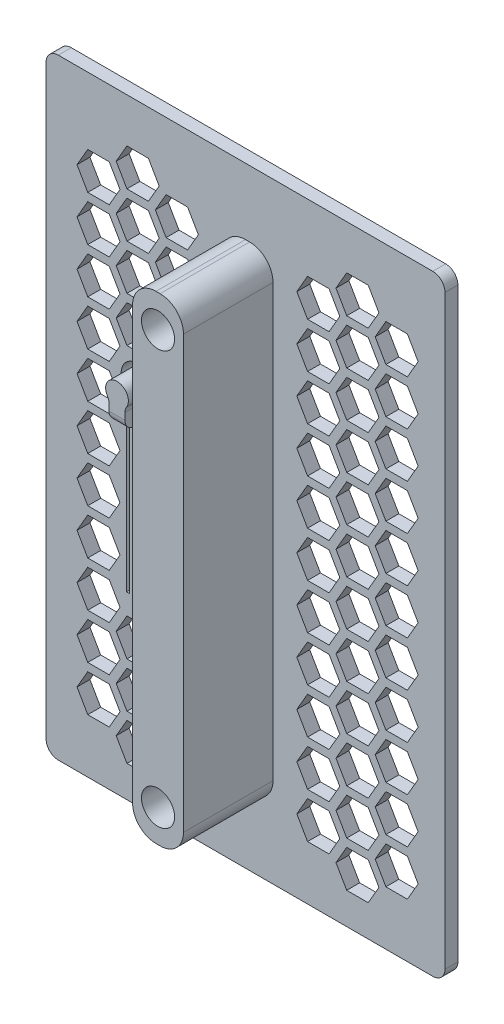
SolidWorks part; units mm, degrees
ref_plane "Front Plane" through (0, 0, 0) normal (0, 0, 1) x (1, 0, 0)
ref_plane "Top Plane" through (0, 0, 0) normal (0, 1, 0) x (1, 0, 0)
ref_plane "Right Plane" through (0, 0, 0) normal (1, 0, 0) x (0, 0, -1)
sketch "Sketch1" plane through (0, 0, 0) normal (0, 0, 1) x (1, 0, 0)
  line L0 (24.5, 37.5) -> (-24.5, 37.5) construction
  line L1 (24.5, -37.5) -> (-24.5, -37.5)
  line L2 (24.5, -37.5) -> (24.5, 37.5)
  line L3 (24.5, 37.5) -> (-24.5, 37.5)
  line L4 (-24.5, -37.5) -> (-24.5, 37.5)
  line L5 (24.5, -37.5) -> (-24.5, 37.5) construction
  line L6 (24.5, 37.5) -> (-24.5, -37.5) construction
  line L7 (24.5, 37.5) -> (24.5, -37.5) construction
  point P0 (0, 0)
extrude "Boss-Extrude1" add sketch "Sketch1" along normal blind 1.5875
sketch "Sketch2" plane through (0, 0, 1.5875) normal (0, 0, 1) x (1, 0, 0)
  line L69 (0, -29.373) -> (0.5, -29.373)
  line L70 (3.373, -26.5) -> (3.373, 26.5)
  line L71 (0.5, 29.373) -> (0, 29.373)
  line L72 (-2.873, 26.5) -> (-2.873, -26.5)
  line L73 (0, -29.373) -> (0.5, -29.373)
  line L74 (3.373, -26.5) -> (3.373, 26.5)
  line L75 (0.5, 29.373) -> (0, 29.373)
  line L76 (-2.873, 26.5) -> (-2.873, -26.5)
  arc A54 (0.5, -29.373) -> (3.373, -26.5) centre (0.5, -26.5) ccw
  arc A55 (-2.873, -26.5) -> (0, -29.373) centre (0, -26.5) ccw
  arc A56 (3.373, 26.5) -> (0.5, 29.373) centre (0.5, 26.5) ccw
  arc A57 (0, 29.373) -> (-2.873, 26.5) centre (0, 26.5) ccw
  arc A58 (0.5, -29.373) -> (3.373, -26.5) centre (0.5, -26.5) ccw
  arc A59 (-2.873, -26.5) -> (0, -29.373) centre (0, -26.5) ccw
  arc A60 (3.373, 26.5) -> (0.5, 29.373) centre (0.5, 26.5) ccw
  arc A61 (0, 29.373) -> (-2.873, 26.5) centre (0, 26.5) ccw
  dimension "D1" = 0.127
extrude "Boss-Extrude2" add sketch "Sketch2" along normal up to surface (11 mm away)
sketch "Sketch3" plane through (0, 0, 12.5875) normal (0, 0, 1) x (1, 0, 0)
  line L0 (0, 29.373) -> (0.5, 29.373) construction
  line L1 (0.25, 25.4) -> (0, 0) construction
  line L2 (0, 0) -> (0.25, -25.4) construction
  circle A0 centre (0.25, 25.4) radius 2.032
  circle A1 centre (0.25, -25.4) radius 2.032
  point P6 (0.25, 29.373)
  dimension "D1" = 4.064
  dimension "D2" = 25.4
extrude "Cut-Extrude1" cut sketch "Sketch3" against normal blind 9.525
fillet "Fillet1" radius 1.5 4 edges at (24.5, -37.5, 0.7937) (-24.5, -37.5, 0.7937) (-24.5, 37.5, 0.7937) (24.5, 37.5, 0.7937)
sketch "Sketch4" plane through (0, 0, 0) normal (0, 0, -1) x (-1, 0, 0)
  line L0 (-18.5619, -28.5679) -> (-13.75, -31.346) construction
  line L1 (-16.3896, -31.346) -> (-15.0698, -33.632)
  line L2 (-15.0698, -33.632) -> (-12.4302, -33.632)
  line L3 (-12.4302, -33.632) -> (-11.1104, -31.346)
  line L4 (-11.1104, -31.346) -> (-12.4302, -29.06)
  line L5 (-12.4302, -29.06) -> (-15.0698, -29.06)
  line L6 (-15.0698, -29.06) -> (-16.3896, -31.346)
  line L7 (-21.2015, -28.5679) -> (-19.8817, -30.8539)
  line L8 (-19.8817, -30.8539) -> (-17.242, -30.8539)
  line L9 (-17.242, -30.8539) -> (-15.9222, -28.5679)
  line L10 (-15.9222, -28.5679) -> (-17.242, -26.2819)
  line L11 (-17.242, -26.2819) -> (-19.8817, -26.2819)
  line L12 (-19.8817, -26.2819) -> (-21.2015, -28.5679)
  line L13 (-10.258, -30.8539) -> (-7.6183, -30.8539)
  line L14 (-7.6183, -30.8539) -> (-6.2985, -28.5679)
  line L15 (-6.2985, -28.5679) -> (-7.6183, -26.2819)
  line L16 (-7.6183, -26.2819) -> (-10.258, -26.2819)
  line L17 (-10.258, -26.2819) -> (-11.5778, -28.5679)
  line L18 (-11.5778, -28.5679) -> (-10.258, -30.8539)
  line L19 (-11.1104, -31.346) -> (-10.258, -30.8539) construction
  line L20 (-13.75, -31.346) -> (-8.9381, -28.5679) construction
  line L21 (-4.5, -26.832) -> (-23, -26.832) construction
  line L22 (-10.258, -20.7257) -> (-11.5778, -23.0117)
  line L23 (-7.6183, -20.7257) -> (-10.258, -20.7257)
  line L24 (-6.2985, -23.0117) -> (-7.6183, -20.7257)
  line L25 (-7.6183, -25.2977) -> (-6.2985, -23.0117)
  line L26 (-10.258, -25.2977) -> (-7.6183, -25.2977)
  line L27 (-11.5778, -23.0117) -> (-10.258, -25.2977)
  line L28 (-11.1104, -25.7898) -> (-12.4302, -23.5038)
  line L29 (-12.4302, -23.5038) -> (-15.0698, -23.5038)
  line L30 (-15.0698, -23.5038) -> (-16.3896, -25.7898)
  line L31 (-16.3896, -25.7898) -> (-15.0698, -28.0758)
  line L32 (-15.0698, -28.0758) -> (-12.4302, -28.0758)
  line L33 (-12.4302, -28.0758) -> (-11.1104, -25.7898)
  line L34 (-17.242, -25.2977) -> (-15.9222, -23.0117)
  line L35 (-15.9222, -23.0117) -> (-17.242, -20.7257)
  line L36 (-17.242, -20.7257) -> (-19.8817, -20.7257)
  line L37 (-19.8817, -20.7257) -> (-21.2015, -23.0117)
  line L38 (-21.2015, -23.0117) -> (-19.8817, -25.2977)
  line L39 (-19.8817, -25.2977) -> (-17.242, -25.2977)
  line L40 (-10.258, -15.1694) -> (-11.5778, -17.4554)
  line L41 (-7.6183, -15.1694) -> (-10.258, -15.1694)
  line L42 (-6.2985, -17.4554) -> (-7.6183, -15.1694)
  line L43 (-7.6183, -19.7414) -> (-6.2985, -17.4554)
  line L44 (-10.258, -19.7414) -> (-7.6183, -19.7414)
  line L45 (-11.5778, -17.4554) -> (-10.258, -19.7414)
  line L46 (-11.1104, -20.2335) -> (-12.4302, -17.9475)
  line L47 (-12.4302, -17.9475) -> (-15.0698, -17.9475)
  line L48 (-15.0698, -17.9475) -> (-16.3896, -20.2335)
  line L49 (-16.3896, -20.2335) -> (-15.0698, -22.5195)
  line L50 (-15.0698, -22.5195) -> (-12.4302, -22.5195)
  line L51 (-12.4302, -22.5195) -> (-11.1104, -20.2335)
  line L52 (-17.242, -19.7414) -> (-15.9222, -17.4554)
  line L53 (-15.9222, -17.4554) -> (-17.242, -15.1694)
  line L54 (-17.242, -15.1694) -> (-19.8817, -15.1694)
  line L55 (-19.8817, -15.1694) -> (-21.2015, -17.4554)
  line L56 (-21.2015, -17.4554) -> (-19.8817, -19.7414)
  line L57 (-19.8817, -19.7414) -> (-17.242, -19.7414)
  line L58 (-10.258, -9.6132) -> (-11.5778, -11.8992)
  line L59 (-7.6183, -9.6132) -> (-10.258, -9.6132)
  line L60 (-6.2985, -11.8992) -> (-7.6183, -9.6132)
  line L61 (-7.6183, -14.1852) -> (-6.2985, -11.8992)
  line L62 (-10.258, -14.1852) -> (-7.6183, -14.1852)
  line L63 (-11.5778, -11.8992) -> (-10.258, -14.1852)
  line L64 (-11.1104, -14.6773) -> (-12.4302, -12.3913)
  line L65 (-12.4302, -12.3913) -> (-15.0698, -12.3913)
  line L66 (-15.0698, -12.3913) -> (-16.3896, -14.6773)
  line L67 (-16.3896, -14.6773) -> (-15.0698, -16.9633)
  line L68 (-15.0698, -16.9633) -> (-12.4302, -16.9633)
  line L69 (-12.4302, -16.9633) -> (-11.1104, -14.6773)
  line L70 (-17.242, -14.1852) -> (-15.9222, -11.8992)
  line L71 (-15.9222, -11.8992) -> (-17.242, -9.6132)
  line L72 (-17.242, -9.6132) -> (-19.8817, -9.6132)
  line L73 (-19.8817, -9.6132) -> (-21.2015, -11.8992)
  line L74 (-21.2015, -11.8992) -> (-19.8817, -14.1852)
  line L75 (-19.8817, -14.1852) -> (-17.242, -14.1852)
  line L76 (-10.258, -4.0569) -> (-11.5778, -6.3429)
  line L77 (-7.6183, -4.0569) -> (-10.258, -4.0569)
  line L78 (-6.2985, -6.3429) -> (-7.6183, -4.0569)
  line L79 (-7.6183, -8.6289) -> (-6.2985, -6.3429)
  line L80 (-10.258, -8.6289) -> (-7.6183, -8.6289)
  line L81 (-11.5778, -6.3429) -> (-10.258, -8.6289)
  line L82 (-11.1104, -9.121) -> (-12.4302, -6.835)
  line L83 (-12.4302, -6.835) -> (-15.0698, -6.835)
  line L84 (-15.0698, -6.835) -> (-16.3896, -9.121)
  line L85 (-16.3896, -9.121) -> (-15.0698, -11.407)
  line L86 (-15.0698, -11.407) -> (-12.4302, -11.407)
  line L87 (-12.4302, -11.407) -> (-11.1104, -9.121)
  line L88 (-17.242, -8.6289) -> (-15.9222, -6.3429)
  line L89 (-15.9222, -6.3429) -> (-17.242, -4.0569)
  line L90 (-17.242, -4.0569) -> (-19.8817, -4.0569)
  line L91 (-19.8817, -4.0569) -> (-21.2015, -6.3429)
  line L92 (-21.2015, -6.3429) -> (-19.8817, -8.6289)
  line L93 (-19.8817, -8.6289) -> (-17.242, -8.6289)
  line L94 (-10.258, 1.4993) -> (-11.5778, -0.7867)
  line L95 (-7.6183, 1.4993) -> (-10.258, 1.4993)
  line L96 (-6.2985, -0.7867) -> (-7.6183, 1.4993)
  line L97 (-7.6183, -3.0727) -> (-6.2985, -0.7867)
  line L98 (-10.258, -3.0727) -> (-7.6183, -3.0727)
  line L99 (-11.5778, -0.7867) -> (-10.258, -3.0727)
  line L100 (-11.1104, -3.5648) -> (-12.4302, -1.2788)
  line L101 (-12.4302, -1.2788) -> (-15.0698, -1.2788)
  line L102 (-15.0698, -1.2788) -> (-16.3896, -3.5648)
  line L103 (-16.3896, -3.5648) -> (-15.0698, -5.8508)
  line L104 (-15.0698, -5.8508) -> (-12.4302, -5.8508)
  line L105 (-12.4302, -5.8508) -> (-11.1104, -3.5648)
  line L106 (-17.242, -3.0727) -> (-15.9222, -0.7867)
  line L107 (-15.9222, -0.7867) -> (-17.242, 1.4993)
  line L108 (-17.242, 1.4993) -> (-19.8817, 1.4993)
  line L109 (-19.8817, 1.4993) -> (-21.2015, -0.7867)
  line L110 (-21.2015, -0.7867) -> (-19.8817, -3.0727)
  line L111 (-19.8817, -3.0727) -> (-17.242, -3.0727)
  line L112 (-10.258, 7.0556) -> (-11.5778, 4.7696)
  line L113 (-7.6183, 7.0556) -> (-10.258, 7.0556)
  line L114 (-6.2985, 4.7696) -> (-7.6183, 7.0556)
  line L115 (-7.6183, 2.4836) -> (-6.2985, 4.7696)
  line L116 (-10.258, 2.4836) -> (-7.6183, 2.4836)
  line L117 (-11.5778, 4.7696) -> (-10.258, 2.4836)
  line L118 (-11.1104, 1.9915) -> (-12.4302, 4.2775)
  line L119 (-12.4302, 4.2775) -> (-15.0698, 4.2775)
  line L120 (-15.0698, 4.2775) -> (-16.3896, 1.9915)
  line L121 (-16.3896, 1.9915) -> (-15.0698, -0.2945)
  line L122 (-15.0698, -0.2945) -> (-12.4302, -0.2945)
  line L123 (-12.4302, -0.2945) -> (-11.1104, 1.9915)
  line L124 (-17.242, 2.4836) -> (-15.9222, 4.7696)
  line L125 (-15.9222, 4.7696) -> (-17.242, 7.0556)
  line L126 (-17.242, 7.0556) -> (-19.8817, 7.0556)
  line L127 (-19.8817, 7.0556) -> (-21.2015, 4.7696)
  line L128 (-21.2015, 4.7696) -> (-19.8817, 2.4836)
  line L129 (-19.8817, 2.4836) -> (-17.242, 2.4836)
  line L130 (-10.258, 12.6118) -> (-11.5778, 10.3258)
  line L131 (-7.6183, 12.6118) -> (-10.258, 12.6118)
  line L132 (-6.2985, 10.3258) -> (-7.6183, 12.6118)
  line L133 (-7.6183, 8.0398) -> (-6.2985, 10.3258)
  line L134 (-10.258, 8.0398) -> (-7.6183, 8.0398)
  line L135 (-11.5778, 10.3258) -> (-10.258, 8.0398)
  line L136 (-11.1104, 7.5477) -> (-12.4302, 9.8337)
  line L137 (-12.4302, 9.8337) -> (-15.0698, 9.8337)
  line L138 (-15.0698, 9.8337) -> (-16.3896, 7.5477)
  line L139 (-16.3896, 7.5477) -> (-15.0698, 5.2617)
  line L140 (-15.0698, 5.2617) -> (-12.4302, 5.2617)
  line L141 (-12.4302, 5.2617) -> (-11.1104, 7.5477)
  line L142 (-17.242, 8.0398) -> (-15.9222, 10.3258)
  line L143 (-15.9222, 10.3258) -> (-17.242, 12.6118)
  line L144 (-17.242, 12.6118) -> (-19.8817, 12.6118)
  line L145 (-19.8817, 12.6118) -> (-21.2015, 10.3258)
  line L146 (-21.2015, 10.3258) -> (-19.8817, 8.0398)
  line L147 (-19.8817, 8.0398) -> (-17.242, 8.0398)
  line L148 (-10.258, 18.1681) -> (-11.5778, 15.8821)
  line L149 (-7.6183, 18.1681) -> (-10.258, 18.1681)
  line L150 (-6.2985, 15.8821) -> (-7.6183, 18.1681)
  line L151 (-7.6183, 13.5961) -> (-6.2985, 15.8821)
  line L152 (-10.258, 13.5961) -> (-7.6183, 13.5961)
  line L153 (-11.5778, 15.8821) -> (-10.258, 13.5961)
  line L154 (-11.1104, 13.104) -> (-12.4302, 15.39)
  line L155 (-12.4302, 15.39) -> (-15.0698, 15.39)
  line L156 (-15.0698, 15.39) -> (-16.3896, 13.104)
  line L157 (-16.3896, 13.104) -> (-15.0698, 10.818)
  line L158 (-15.0698, 10.818) -> (-12.4302, 10.818)
  line L159 (-12.4302, 10.818) -> (-11.1104, 13.104)
  line L160 (-17.242, 13.5961) -> (-15.9222, 15.8821)
  line L161 (-15.9222, 15.8821) -> (-17.242, 18.1681)
  line L162 (-17.242, 18.1681) -> (-19.8817, 18.1681)
  line L163 (-19.8817, 18.1681) -> (-21.2015, 15.8821)
  line L164 (-21.2015, 15.8821) -> (-19.8817, 13.5961)
  line L165 (-19.8817, 13.5961) -> (-17.242, 13.5961)
  line L166 (-10.258, 23.7243) -> (-11.5778, 21.4383)
  line L167 (-7.6183, 23.7243) -> (-10.258, 23.7243)
  line L168 (-6.2985, 21.4383) -> (-7.6183, 23.7243)
  line L169 (-7.6183, 19.1523) -> (-6.2985, 21.4383)
  line L170 (-10.258, 19.1523) -> (-7.6183, 19.1523)
  line L171 (-11.5778, 21.4383) -> (-10.258, 19.1523)
  line L172 (-11.1104, 18.6602) -> (-12.4302, 20.9462)
  line L173 (-12.4302, 20.9462) -> (-15.0698, 20.9462)
  line L174 (-15.0698, 20.9462) -> (-16.3896, 18.6602)
  line L175 (-16.3896, 18.6602) -> (-15.0698, 16.3742)
  line L176 (-15.0698, 16.3742) -> (-12.4302, 16.3742)
  line L177 (-12.4302, 16.3742) -> (-11.1104, 18.6602)
  line L178 (-17.242, 19.1523) -> (-15.9222, 21.4383)
  line L179 (-15.9222, 21.4383) -> (-17.242, 23.7243)
  line L180 (-17.242, 23.7243) -> (-19.8817, 23.7243)
  line L181 (-19.8817, 23.7243) -> (-21.2015, 21.4383)
  line L182 (-21.2015, 21.4383) -> (-19.8817, 19.1523)
  line L183 (-19.8817, 19.1523) -> (-17.242, 19.1523)
  line L202 (-11.5778, -28.5679) -> (-12.4302, -28.0758) construction
  line L203 (-0.25, 29.373) -> (-0.25, -29.5) construction
  line L204 (0, 29.373) -> (-0.5, 29.373) construction
  line L205 (0, -29.5) -> (-0.5, -29.5) construction
  line L206 (11.0778, -28.5679) -> (11.9302, -28.0758) construction
  line L207 (13.25, -31.346) -> (8.4381, -28.5679) construction
  line L208 (10.6104, -31.346) -> (9.758, -30.8539) construction
  line L209 (18.0619, -28.5679) -> (13.25, -31.346) construction
  line L228 (19.3817, 19.1523) -> (16.742, 19.1523)
  line L229 (20.7015, 21.4383) -> (19.3817, 19.1523)
  line L230 (19.3817, 23.7243) -> (20.7015, 21.4383)
  line L231 (16.742, 23.7243) -> (19.3817, 23.7243)
  line L232 (15.4222, 21.4383) -> (16.742, 23.7243)
  line L233 (16.742, 19.1523) -> (15.4222, 21.4383)
  line L234 (11.9302, 16.3742) -> (10.6104, 18.6602)
  line L235 (14.5698, 16.3742) -> (11.9302, 16.3742)
  line L236 (15.8896, 18.6602) -> (14.5698, 16.3742)
  line L237 (14.5698, 20.9462) -> (15.8896, 18.6602)
  line L238 (11.9302, 20.9462) -> (14.5698, 20.9462)
  line L239 (10.6104, 18.6602) -> (11.9302, 20.9462)
  line L240 (11.0778, 21.4383) -> (9.758, 19.1523)
  line L241 (9.758, 19.1523) -> (7.1183, 19.1523)
  line L242 (7.1183, 19.1523) -> (5.7985, 21.4383)
  line L243 (5.7985, 21.4383) -> (7.1183, 23.7243)
  line L244 (7.1183, 23.7243) -> (9.758, 23.7243)
  line L245 (9.758, 23.7243) -> (11.0778, 21.4383)
  line L246 (19.3817, 13.5961) -> (16.742, 13.5961)
  line L247 (20.7015, 15.8821) -> (19.3817, 13.5961)
  line L248 (19.3817, 18.1681) -> (20.7015, 15.8821)
  line L249 (16.742, 18.1681) -> (19.3817, 18.1681)
  line L250 (15.4222, 15.8821) -> (16.742, 18.1681)
  line L251 (16.742, 13.5961) -> (15.4222, 15.8821)
  line L258 (11.0778, 15.8821) -> (9.758, 13.5961)
  line L259 (9.758, 13.5961) -> (7.1183, 13.5961)
  line L260 (7.1183, 13.5961) -> (5.7985, 15.8821)
  line L261 (5.7985, 15.8821) -> (7.1183, 18.1681)
  line L262 (7.1183, 18.1681) -> (9.758, 18.1681)
  line L263 (9.758, 18.1681) -> (11.0778, 15.8821)
  line L264 (19.3817, 8.0398) -> (16.742, 8.0398)
  line L265 (20.7015, 10.3258) -> (19.3817, 8.0398)
  line L266 (19.3817, 12.6118) -> (20.7015, 10.3258)
  line L267 (16.742, 12.6118) -> (19.3817, 12.6118)
  line L268 (15.4222, 10.3258) -> (16.742, 12.6118)
  line L269 (16.742, 8.0398) -> (15.4222, 10.3258)
  line L276 (11.0778, 10.3258) -> (9.758, 8.0398)
  line L277 (9.758, 8.0398) -> (7.1183, 8.0398)
  line L278 (7.1183, 8.0398) -> (5.7985, 10.3258)
  line L279 (5.7985, 10.3258) -> (7.1183, 12.6118)
  line L280 (7.1183, 12.6118) -> (9.758, 12.6118)
  line L281 (9.758, 12.6118) -> (11.0778, 10.3258)
  line L282 (19.3817, 2.4836) -> (16.742, 2.4836)
  line L283 (20.7015, 4.7696) -> (19.3817, 2.4836)
  line L284 (19.3817, 7.0556) -> (20.7015, 4.7696)
  line L285 (16.742, 7.0556) -> (19.3817, 7.0556)
  line L286 (15.4222, 4.7696) -> (16.742, 7.0556)
  line L287 (16.742, 2.4836) -> (15.4222, 4.7696)
  line L294 (11.0778, 4.7696) -> (9.758, 2.4836)
  line L295 (9.758, 2.4836) -> (7.1183, 2.4836)
  line L296 (7.1183, 2.4836) -> (5.7985, 4.7696)
  line L297 (5.7985, 4.7696) -> (7.1183, 7.0556)
  line L298 (7.1183, 7.0556) -> (9.758, 7.0556)
  line L299 (9.758, 7.0556) -> (11.0778, 4.7696)
  line L300 (19.3817, -3.0727) -> (16.742, -3.0727)
  line L301 (20.7015, -0.7867) -> (19.3817, -3.0727)
  line L302 (19.3817, 1.4993) -> (20.7015, -0.7867)
  line L303 (16.742, 1.4993) -> (19.3817, 1.4993)
  line L304 (15.4222, -0.7867) -> (16.742, 1.4993)
  line L305 (16.742, -3.0727) -> (15.4222, -0.7867)
  line L312 (11.0778, -0.7867) -> (9.758, -3.0727)
  line L313 (9.758, -3.0727) -> (7.1183, -3.0727)
  line L314 (7.1183, -3.0727) -> (5.7985, -0.7867)
  line L315 (5.7985, -0.7867) -> (7.1183, 1.4993)
  line L316 (7.1183, 1.4993) -> (9.758, 1.4993)
  line L317 (9.758, 1.4993) -> (11.0778, -0.7867)
  line L318 (19.3817, -8.6289) -> (16.742, -8.6289)
  line L319 (20.7015, -6.3429) -> (19.3817, -8.6289)
  line L320 (19.3817, -4.0569) -> (20.7015, -6.3429)
  line L321 (16.742, -4.0569) -> (19.3817, -4.0569)
  line L322 (15.4222, -6.3429) -> (16.742, -4.0569)
  line L323 (16.742, -8.6289) -> (15.4222, -6.3429)
  line L330 (11.0778, -6.3429) -> (9.758, -8.6289)
  line L331 (9.758, -8.6289) -> (7.1183, -8.6289)
  line L332 (7.1183, -8.6289) -> (5.7985, -6.3429)
  line L333 (5.7985, -6.3429) -> (7.1183, -4.0569)
  line L334 (7.1183, -4.0569) -> (9.758, -4.0569)
  line L335 (9.758, -4.0569) -> (11.0778, -6.3429)
  line L336 (19.3817, -14.1852) -> (16.742, -14.1852)
  line L337 (20.7015, -11.8992) -> (19.3817, -14.1852)
  line L338 (19.3817, -9.6132) -> (20.7015, -11.8992)
  line L339 (16.742, -9.6132) -> (19.3817, -9.6132)
  line L340 (15.4222, -11.8992) -> (16.742, -9.6132)
  line L341 (16.742, -14.1852) -> (15.4222, -11.8992)
  line L348 (11.0778, -11.8992) -> (9.758, -14.1852)
  line L349 (9.758, -14.1852) -> (7.1183, -14.1852)
  line L350 (7.1183, -14.1852) -> (5.7985, -11.8992)
  line L351 (5.7985, -11.8992) -> (7.1183, -9.6132)
  line L352 (7.1183, -9.6132) -> (9.758, -9.6132)
  line L353 (9.758, -9.6132) -> (11.0778, -11.8992)
  line L354 (19.3817, -19.7414) -> (16.742, -19.7414)
  line L355 (20.7015, -17.4554) -> (19.3817, -19.7414)
  line L356 (19.3817, -15.1694) -> (20.7015, -17.4554)
  line L357 (16.742, -15.1694) -> (19.3817, -15.1694)
  line L358 (15.4222, -17.4554) -> (16.742, -15.1694)
  line L359 (16.742, -19.7414) -> (15.4222, -17.4554)
  line L366 (11.0778, -17.4554) -> (9.758, -19.7414)
  line L367 (9.758, -19.7414) -> (7.1183, -19.7414)
  line L368 (7.1183, -19.7414) -> (5.7985, -17.4554)
  line L369 (5.7985, -17.4554) -> (7.1183, -15.1694)
  line L370 (7.1183, -15.1694) -> (9.758, -15.1694)
  line L371 (9.758, -15.1694) -> (11.0778, -17.4554)
  line L372 (19.3817, -25.2977) -> (16.742, -25.2977)
  line L373 (20.7015, -23.0117) -> (19.3817, -25.2977)
  line L374 (19.3817, -20.7257) -> (20.7015, -23.0117)
  line L375 (16.742, -20.7257) -> (19.3817, -20.7257)
  line L376 (15.4222, -23.0117) -> (16.742, -20.7257)
  line L377 (16.742, -25.2977) -> (15.4222, -23.0117)
  line L378 (11.9302, -28.0758) -> (10.6104, -25.7898)
  line L379 (14.5698, -28.0758) -> (11.9302, -28.0758)
  line L380 (15.8896, -25.7898) -> (14.5698, -28.0758)
  line L381 (14.5698, -23.5038) -> (15.8896, -25.7898)
  line L382 (11.9302, -23.5038) -> (14.5698, -23.5038)
  line L383 (10.6104, -25.7898) -> (11.9302, -23.5038)
  line L384 (11.0778, -23.0117) -> (9.758, -25.2977)
  line L385 (9.758, -25.2977) -> (7.1183, -25.2977)
  line L386 (7.1183, -25.2977) -> (5.7985, -23.0117)
  line L387 (5.7985, -23.0117) -> (7.1183, -20.7257)
  line L388 (7.1183, -20.7257) -> (9.758, -20.7257)
  line L389 (9.758, -20.7257) -> (11.0778, -23.0117)
  line L390 (11.0778, -28.5679) -> (9.758, -30.8539)
  line L391 (9.758, -26.2819) -> (11.0778, -28.5679)
  line L392 (7.1183, -26.2819) -> (9.758, -26.2819)
  line L393 (5.7985, -28.5679) -> (7.1183, -26.2819)
  line L394 (7.1183, -30.8539) -> (5.7985, -28.5679)
  line L395 (9.758, -30.8539) -> (7.1183, -30.8539)
  line L396 (19.3817, -26.2819) -> (20.7015, -28.5679)
  line L397 (16.742, -26.2819) -> (19.3817, -26.2819)
  line L398 (15.4222, -28.5679) -> (16.742, -26.2819)
  line L399 (16.742, -30.8539) -> (15.4222, -28.5679)
  line L400 (19.3817, -30.8539) -> (16.742, -30.8539)
  line L401 (20.7015, -28.5679) -> (19.3817, -30.8539)
  line L402 (14.5698, -29.06) -> (15.8896, -31.346)
  line L403 (11.9302, -29.06) -> (14.5698, -29.06)
  line L404 (10.6104, -31.346) -> (11.9302, -29.06)
  line L405 (11.9302, -33.632) -> (10.6104, -31.346)
  line L406 (14.5698, -33.632) -> (11.9302, -33.632)
  line L407 (15.8896, -31.346) -> (14.5698, -33.632)
  line L408 (11.0778, -11.8992) -> (11.8715, -11.8992) construction
  line L409 (11.9302, 10.818) -> (10.6104, 13.104)
  line L410 (16.742, -14.1852) -> (16.742, -15.1694) construction
  line L417 (10.6104, 13.104) -> (11.9302, 15.39)
  line L418 (11.9302, 15.39) -> (14.5698, 15.39)
  line L419 (-10.258, 29.2806) -> (-11.5778, 26.9946)
  line L426 (-7.6183, 29.2806) -> (-10.258, 29.2806)
  line L427 (-6.2985, 26.9946) -> (-7.6183, 29.2806)
  line L434 (-7.6183, 24.7086) -> (-6.2985, 26.9946)
  line L435 (11.9302, -22.5195) -> (10.6104, -20.2335)
  line L436 (14.5698, -22.5195) -> (11.9302, -22.5195)
  line L437 (15.8896, -20.2335) -> (14.5698, -22.5195)
  line L438 (14.5698, -17.9475) -> (15.8896, -20.2335)
  line L439 (11.9302, -17.9475) -> (14.5698, -17.9475)
  line L440 (10.6104, -20.2335) -> (11.9302, -17.9475)
  line L441 (-4.5, -21.3426) -> (-4.5, -12.1527) construction
  line L442 (-23, -37.5) -> (23, -37.5) construction
  line L443 (-23, -12.7255) -> (-23, -21.3426) construction
  line L444 (-10.258, 24.7086) -> (-7.6183, 24.7086)
  line L445 (-11.5778, 26.9946) -> (-10.258, 24.7086)
  line L446 (-11.1104, 24.2165) -> (-12.4302, 26.5025)
  line L447 (-12.4302, 26.5025) -> (-15.0698, 26.5025)
  line L448 (-15.0698, 26.5025) -> (-16.3896, 24.2165)
  line L449 (-16.3896, 24.2165) -> (-15.0698, 21.9305)
  line L450 (-15.0698, 21.9305) -> (-12.4302, 21.9305)
  line L451 (-12.4302, 21.9305) -> (-11.1104, 24.2165)
  line L452 (-17.242, 24.7086) -> (-15.9222, 26.9946)
  line L453 (-15.9222, 26.9946) -> (-17.242, 29.2806)
  line L454 (-17.242, 29.2806) -> (-19.8817, 29.2806)
  line L455 (-19.8817, 29.2806) -> (-21.2015, 26.9946)
  line L456 (-21.2015, 26.9946) -> (-19.8817, 24.7086)
  line L457 (-19.8817, 24.7086) -> (-17.242, 24.7086)
  line L458 (7.1183, 24.7086) -> (5.7985, 26.9946)
  line L459 (5.7985, 26.9946) -> (7.1183, 29.2806)
  line L460 (7.1183, 29.2806) -> (9.758, 29.2806)
  line L461 (9.758, 29.2806) -> (11.0778, 26.9946)
  line L462 (11.0778, 26.9946) -> (9.758, 24.7086)
  line L463 (9.758, 24.7086) -> (7.1183, 24.7086)
  line L464 (15.8896, 24.2165) -> (14.5698, 21.9305)
  line L465 (14.5698, 21.9305) -> (11.9302, 21.9305)
  line L466 (11.9302, 21.9305) -> (10.6104, 24.2165)
  line L467 (10.6104, 24.2165) -> (11.9302, 26.5025)
  line L468 (11.9302, 26.5025) -> (14.5698, 26.5025)
  line L469 (14.5698, 26.5025) -> (15.8896, 24.2165)
  line L470 (20.7015, 26.9946) -> (19.3817, 24.7086)
  line L471 (19.3817, 29.2806) -> (20.7015, 26.9946)
  line L472 (16.742, 29.2806) -> (19.3817, 29.2806)
  line L473 (15.4222, 26.9946) -> (16.742, 29.2806)
  line L474 (16.742, 24.7086) -> (15.4222, 26.9946)
  line L475 (19.3817, 24.7086) -> (16.742, 24.7086)
  line L476 (15.4222, -11.8992) -> (14.6285, -11.8992) construction
  line L477 (9.758, 8.0398) -> (9.758, 7.0556) construction
  line L478 (14.5698, 15.39) -> (15.8896, 13.104)
  line L479 (15.8896, 13.104) -> (14.5698, 10.818)
  line L480 (14.5698, 10.818) -> (11.9302, 10.818)
  line L481 (11.8715, -15.4075) -> (11.8715, 6.0548)
  line L483 (12.2684, 6.5537) -> (12.2684, -15.4075)
  line L484 (12.2684, -15.4075) -> (11.8715, -15.4075)
  line L485 (14.2316, -15.4075) -> (14.6285, -15.4075)
  line L486 (14.6285, -15.4075) -> (14.6285, 6.0548)
  line L488 (14.2316, 6.5537) -> (14.2316, -15.4075)
  line L489 (-13.75, 27.4867) -> (-13.75, 26.5025) construction
  line L490 (20.5, -36.3947) -> (22.625, -36.3947) construction
  line L491 (-16.5821, 28.1376) -> (-15.7297, 28.6297) construction
  line L492 (-11.1104, 29.7727) -> (-12.4302, 32.0587)
  line L493 (-12.4302, 32.0587) -> (-15.0698, 32.0587)
  line L494 (-15.0698, 32.0587) -> (-16.3896, 29.7727)
  line L495 (-16.3896, 29.7727) -> (-15.0698, 27.4867)
  line L496 (-15.0698, 27.4867) -> (-12.4302, 27.4867)
  line L497 (-12.4302, 27.4867) -> (-11.1104, 29.7727)
  line L498 (10.4179, 28.1376) -> (11.2703, 28.6297) construction
  line L499 (10.6104, 29.7727) -> (11.9302, 27.4867)
  line L500 (11.9302, 27.4867) -> (14.5698, 27.4867)
  line L501 (14.5698, 27.4867) -> (15.8896, 29.7727)
  line L502 (15.8896, 29.7727) -> (14.5698, 32.0587)
  line L503 (14.5698, 32.0587) -> (11.9302, 32.0587)
  line L504 (11.9302, 32.0587) -> (10.6104, 29.7727)
  line L505 (13.25, 26.5025) -> (13.25, 27.4867) construction
  circle A0 centre (-13.75, -31.346) radius 2.286 construction
  circle A1 centre (-18.5619, -28.5679) radius 2.286 construction
  circle A2 centre (-8.9381, -28.5679) radius 2.286 construction
  circle A3 centre (8.4381, -28.5679) radius 2.286 construction
  circle A4 centre (18.0619, -28.5679) radius 2.286 construction
  circle A5 centre (13.25, -31.346) radius 2.286 construction
  arc A9 (12.2684, 6.5537) -> (14.2316, 6.5537) centre (13.25, 7.5477) cw
  arc A10 (11.8715, 6.0548) -> (14.6285, 6.0548) centre (13.25, 7.5477) cw
  circle A11 centre (-13.75, 29.7727) radius 2.286 construction
  circle A12 centre (13.25, 29.7727) radius 2.286 construction
  point P28 (-13.75, -26.832)
  point P341 (9.758, 7.5477)
  dimension "D1" = 4.572
  dimension "D7" = 2.54
  dimension "D9" = 0.635
  dimension "D10" = 2.032
  dimension "D2" = 5.5562
  dimension "D3" = 4.514
  dimension "D5" = 0.3969
  dimension "D6" = 0.7937
  dimension "D8" = 10.668
  dimension "D11" = 43.9424
  dimension "D4" = 11
extrude "Cut-Extrude2" cut sketch "Sketch4" against normal through all
sketch "Sketch5" plane through (0, 0, 1.5875) normal (0, 0, 1) x (1, 0, 0)
  line L5 (-14.2316, 6.5537) -> (-14.2316, 4.0137)
  line L6 (-14.2316, -15.4075) -> (-14.2316, 6.5537) construction
  line L7 (-14.2316, 4.0137) -> (-12.2684, 4.0137)
  line L8 (-12.2684, 6.5537) -> (-12.2684, -15.4075) construction
  line L9 (-12.2684, 4.0137) -> (-12.2684, 6.5537)
  arc A2 (-12.2684, 6.5537) -> (-14.2316, 6.5537) centre (-13.25, 7.5477) ccw construction
  arc A3 (-12.2684, 6.5537) -> (-14.2316, 6.5537) centre (-13.25, 7.5477) ccw
  dimension "D2" = 2.54
extrude "Boss-Extrude3" add sketch "Sketch5" along normal blind 2.54
fillet "Fillet2" radius 1.27 6 edges at (-13.25, 4.0137, 4.1275) (-13.25, 4.0137, 1.5875) (-14.6285, 6.0548, 0.7938) (-11.8715, 6.0548, 0.7938) (-14.2316, 6.5537, 2.0638) (-12.2684, 6.5537, 2.0638)
